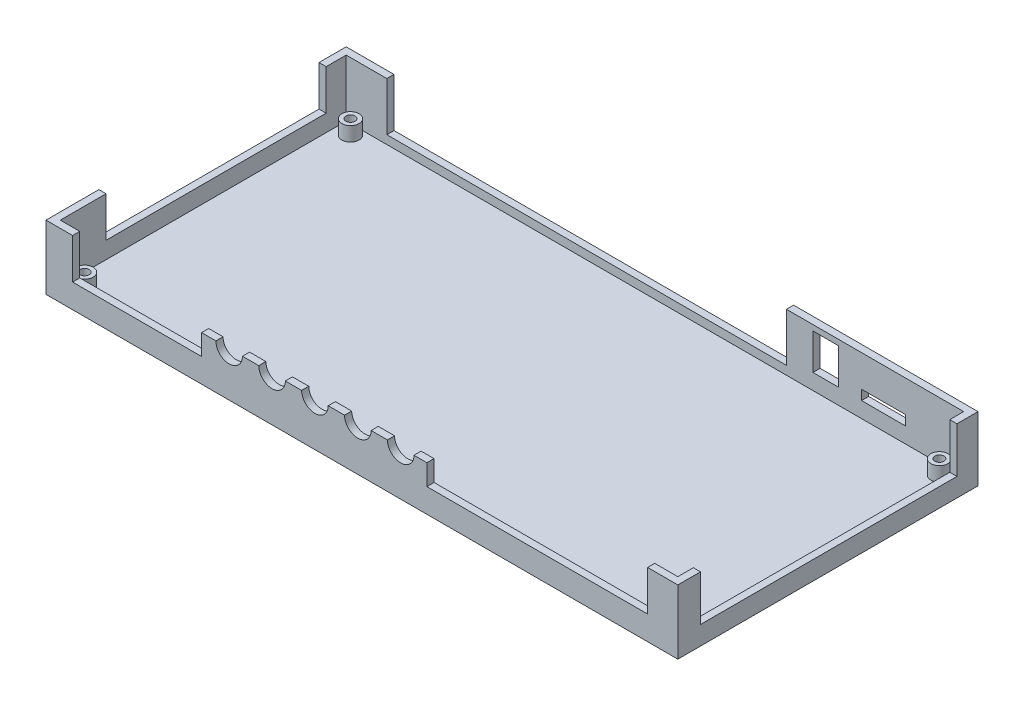
SolidWorks part; units mm, degrees
ref_plane "Front Plane" through (0, 0, 0) normal (0, 0, 1) x (1, 0, 0)
ref_plane "Top Plane" through (0, 0, 0) normal (0, 1, 0) x (1, 0, 0)
ref_plane "Right Plane" through (0, 0, 0) normal (1, 0, 0) x (0, 0, -1)
sketch "Sketch1" plane through (0, 0, 0) normal (0, 1, 0) x (1, 0, 0)
  line L0 (-110.5, -52.5) -> (-110.5, 52.5)
  line L1 (-108, -50) -> (108, -50)
  line L2 (-108, -50) -> (-108, 50)
  line L3 (-108, 50) -> (108, 50)
  line L4 (108, -50) -> (108, 50)
  line L5 (-108, -50) -> (108, 50) construction
  line L6 (-108, 50) -> (108, -50) construction
  line L7 (-110.5, 52.5) -> (110.5, 52.5)
  line L8 (110.5, -52.5) -> (110.5, 52.5)
  line L9 (-110.5, -52.5) -> (110.5, -52.5)
  point P0 (0, 0)
  dimension "D1" = 216
  dimension "D2" = 100
  dimension "D3" = 2.5
extrude "Boss-Extrude1" add sketch "Sketch1" along normal blind 20 contours L0 L9 L8 L7 L4 L1 L2 L3 region at (-108.0532, 0, 0)
extrude "Boss-Extrude2" add sketch "Sketch1<3>" against normal blind 2.5 contours L0 L7 L8 L9
sketch "Sketch1<3>" plane through (0, 0, 0) normal (0, 1, 0) x (1, 0, 0) same geometry as "Sketch1"
ref_plane "Plane1" through (-110.5, 20, 52.5) normal (1, 0, 0) x (0, 0, -1)
sketch "Sketch3" plane through (0, 0, 52.5) normal (0, 0, 1) x (1, 0, 0)
  line L0 (-110.5, 20) -> (110.5, 20) construction
  line L1 (-101.2008, 20) -> (99.9204, 20)
  line L2 (-101.2008, 20) -> (-101.2008, 5.8947)
  line L3 (-101.2008, 5.8947) -> (99.9204, 5.8947)
  line L4 (99.9204, 20) -> (99.9204, 5.8947)
extrude "Cut-Extrude1" cut sketch "Sketch3" against normal blind 10
sketch "Sketch4" plane through (110.5, 0, 0) normal (1, 0, 0) x (0, 0, -1)
  line L0 (-52.5, 20) -> (52.5, 20) construction
  line L1 (-44.5761, 20) -> (45.1289, 20)
  line L2 (-44.5761, 20) -> (-44.5761, 4.0461)
  line L3 (-44.5761, 4.0461) -> (45.1289, 4.0461)
  line L4 (45.1289, 20) -> (45.1289, 4.0461)
extrude "Cut-Extrude2" cut sketch "Sketch4" against normal blind 10
sketch "Sketch5" plane through (0, 0, 52.5) normal (0, 0, 1) x (1, 0, 0)
  line L0 (-144.165, 13.1347) -> (142.8743, 13.1347) construction
  line L1 (-101.2008, 5.8947) -> (99.9204, 5.8947) construction
  line L2 (0, -12.375) -> (0, 12.375) construction
  line L4 (-56.08, 5.8947) -> (22.72, 5.8947)
  line L6 (-41.78, 13.1347) -> (-36.08, 13.1347)
  line L7 (-26.78, 13.1347) -> (-21.08, 13.1347)
  line L8 (-11.78, 13.1347) -> (-6.08, 13.1347)
  line L9 (3.22, 13.1347) -> (8.92, 13.1347)
  line L10 (-56.08, 13.1347) -> (-56.08, 5.8947)
  line L11 (-56.08, 13.1347) -> (-51.08, 13.1347)
  line L12 (22.72, 13.1347) -> (22.72, 5.8947)
  line L13 (18.22, 13.1347) -> (22.72, 13.1347)
  circle A0 centre (-46.43, 13.1347) radius 4.65 construction
  circle A1 centre (-31.43, 13.1347) radius 4.65 construction
  circle A2 centre (-16.43, 13.1347) radius 4.65 construction
  circle A3 centre (-1.43, 13.1347) radius 4.65 construction
  circle A4 centre (13.57, 13.1347) radius 4.65 construction
  arc A5 (-51.08, 13.1347) -> (-41.78, 13.1347) centre (-46.43, 13.1347) ccw
  arc A6 (-36.08, 13.1347) -> (-26.78, 13.1347) centre (-31.43, 13.1347) ccw
  arc A7 (-21.08, 13.1347) -> (-11.78, 13.1347) centre (-16.43, 13.1347) ccw
  arc A8 (-6.08, 13.1347) -> (3.22, 13.1347) centre (-1.43, 13.1347) ccw
  arc A9 (8.92, 13.1347) -> (18.22, 13.1347) centre (13.57, 13.1347) ccw
  point P4 (-46.43, 13.1347)
  point P5 (-31.43, 13.1347)
  point P6 (-16.43, 13.1347)
  point P7 (-1.43, 13.1347)
  point P8 (13.57, 13.1347)
  dimension "D7" = 9.3
  dimension "D8" = 5
  dimension "D9" = 4.5
  dimension "D1" = 7.24
  dimension "D2" = 46.43
  dimension "D3" = 31.43
  dimension "D4" = 16.43
  dimension "D5" = 1.43
  dimension "D6" = 13.57
extrude "Boss-Extrude3" add sketch "Sketch5" against normal up to surface (2.5 mm away) up to face at (-0.3201, 11.4737, 50)
sketch "Sketch6" plane through (0, 0, -52.5) normal (0, 0, -1) x (-1, 0, 0)
  line L0 (110.5, 20) -> (-110.5, 20) construction
  line L1 (-46, 20) -> (46, 20)
  line L2 (-46, 20) -> (-46, 3)
  line L3 (-46, 3) -> (46, 3)
  line L4 (46, 20) -> (46, 3)
  line L5 (0, 12.375) -> (0, -12.375) construction
  dimension "D1" = 92
  dimension "D2" = 46
  dimension "D3" = 17
extrude "Cut-Extrude3" cut sketch "Sketch6" against normal blind 10
sketch "Sketch7" plane through (-110.5, 0, 0) normal (-1, 0, 0) x (0, 0, 1)
  line L0 (52.5, 20) -> (-52.5, 20) construction
  line L1 (34, 20) -> (-43, 20)
  line L2 (34, 20) -> (34, 5.9)
  line L3 (34, 5.9) -> (-43, 5.9)
  line L4 (-43, 20) -> (-43, 5.9)
  line L5 (52.5, 20) -> (52.5, -2.5) construction
  line L6 (52.5, -2.5) -> (-52.5, -2.5) construction
  dimension "D1" = 18.5
  dimension "D2" = 7
  dimension "D3" = 8.4
extrude "Cut-Extrude4" cut sketch "Sketch7" against normal blind 10
sketch "Sketch8" plane through (0, 0, -52.5) normal (0, 0, -1) x (-1, 0, 0)
  line L0 (110.5, 20) -> (46, 20) construction
  line L1 (45.2316, 20) -> (93.7751, 20)
  line L2 (45.2316, 20) -> (45.2316, 3)
  line L3 (45.2316, 3) -> (93.7751, 3)
  line L4 (93.7751, 20) -> (93.7751, 3)
  line L5 (-46, 3) -> (46, 3) construction
extrude "Cut-Extrude5" cut sketch "Sketch8" against normal blind 4
sketch "Sketch9" plane through (0, 0, -50) normal (0, 0, 1) x (1, 0, 0)
  line L1 (72.2471, 8.9082) -> (87.6268, 8.9082)
  line L2 (72.2471, 8.9082) -> (72.2471, 5.4667)
  line L3 (72.2471, 5.4667) -> (87.6268, 5.4667)
  line L4 (87.6268, 8.9082) -> (87.6268, 5.4667)
extrude "Cut-Extrude6" cut sketch "Sketch9" against normal blind 4
sketch "Sketch10" plane through (0, 0, -50) normal (0, 0, 1) x (1, 0, 0)
  line L1 (55.2825, 18.0604) -> (64.1512, 18.0604)
  line L2 (55.2825, 18.0604) -> (55.2825, 5.4968)
  line L3 (55.2825, 5.4968) -> (64.1512, 5.4968)
  line L4 (64.1512, 18.0604) -> (64.1512, 5.4968)
extrude "Cut-Extrude7" cut sketch "Sketch10" against normal blind 4
sketch "Sketch11" plane through (0, -2.5, 0) normal (0, -1, 0) x (1, 0, 0)
  line L0 (0, -12.375) -> (0, 12.375) construction
  line L1 (-103, 46.5) -> (103, 46.5)
  line L2 (-103, 46.5) -> (-103, -46.5)
  line L3 (-103, -46.5) -> (103, -46.5)
  line L4 (103, 46.5) -> (103, -46.5)
  dimension "D1" = 206
  dimension "D2" = 93
  dimension "D3" = 103
  dimension "D4" = 46.5
sketch "Sketch15" plane through (0, 0, 0) normal (0, 1, 0) x (1, 0, 0)
  line L0 (-103, -46.5) -> (103, -46.5) construction
  line L1 (103, -46.5) -> (103, 46.5) construction
  line L2 (-103, 46.5) -> (103, 46.5) construction
  line L3 (-103, -46.5) -> (-103, 46.5) construction
  line L4 (-103, -46.5) -> (103, -46.5)
  line L5 (103, -46.5) -> (103, 46.5)
  line L6 (-103, 46.5) -> (103, 46.5)
  line L7 (-103, -46.5) -> (-103, 46.5)
  circle A0 centre (-103, 46.5) radius 3
  circle A1 centre (103, 46.5) radius 3
  circle A2 centre (103, -46.5) radius 3
  circle A4 centre (-103, -46.5) radius 3
  dimension "D1" = 6
extrude "Boss-Extrude4" add sketch "Sketch15" along normal blind 5 contours L6 A0 L7 | L7 A0 L6 | L7 A4 L4 | L4 A4 L7 | L4 A2 L5 | L5 A2 L4 | L5 A1 L6 | L6 A1 L5 region at (-101.7268, 0, 45.2268) region at (-103.4244, 0, 46.9244) region at (101.7268, 0, 45.2268) region at (103.4244, 0, 46.9244) region at (-103.4244, 0, -46.9244) region at (-101.7268, 0, -45.2268) region at (101.7268, 0, -45.2268) region at (103.4244, 0, -46.9244)
hole_wizard "CBORE for M3 Hex Head Cap Screw1" positions "Sketch12" profile "Sketch14" counterbore size "M3" standard "ISO"
sketch "Sketch12" plane through (0, -2.5, 0) normal (0, -1, 0) x (-1, 0, 0)
  point P0 (103, -46.5)
  point P3 (-103, -46.5)
  point P6 (-103, 46.5)
  point P9 (103, 46.5)
sketch "Sketch14" plane through (-103, -2.5, 46.5) normal (1, 0, 0) x (0, 0, -1)
  line L0 (0, 0) -> (0, 11.0614)
  line L1 (0, 11.0614) -> (1.6, 10.1)
  line L2 (1.6, 10.1) -> (1.6, 2.5)
  line L3 (1.6, 2.5) -> (2.75, 2.5)
  line L4 (2.75, 2.5) -> (2.75, 0)
  line L5 (2.75, 0) -> (0, 0)
  line L10 (0, 11.0614) -> (-1.6, 10.1) construction
  line L11 (0, -6.35) -> (0, 107.95) construction
  dimension "Hole Dia." = 3.2
  dimension "Hole Depth" = 10.1
  dimension "C'Bore Dia." = 5.5
  dimension "C'Bore Depth" = 2.5
  dimension "Drill Angle" = 118
equation "\"D2@Sketch6\"=\"D1@Sketch6\"/2"
equation "\"D3@Sketch11\"=\"D1@Sketch11\"/2"
equation "\"D4@Sketch11\"=\"D2@Sketch11\"/2"
